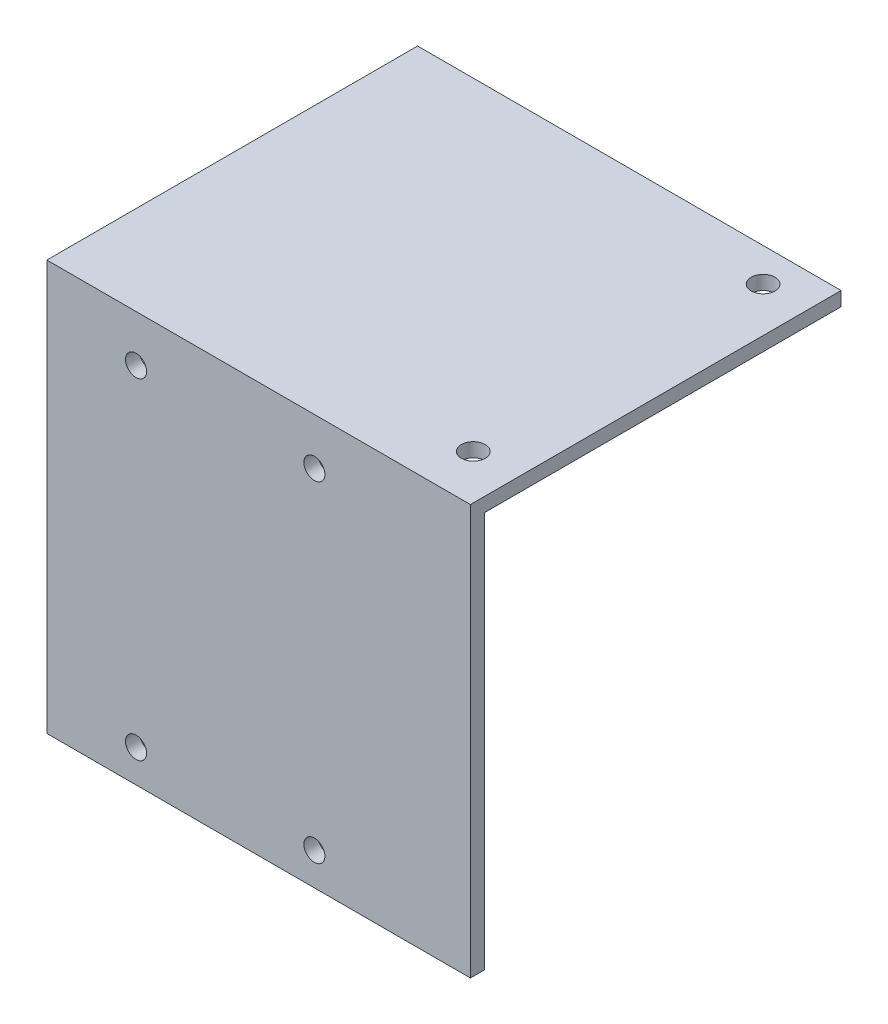
SolidWorks part; units mm, degrees
ref_plane "Front Plane" through (0, 0, 0) normal (0, 0, 1) x (1, 0, 0)
ref_plane "Top Plane" through (0, 0, 0) normal (0, 1, 0) x (1, 0, 0)
ref_plane "Right Plane" through (0, 0, 0) normal (1, 0, 0) x (0, 0, -1)
sketch "Sketch1" plane through (0, 0, 0) normal (0, 0, 1) x (1, 0, 0)
  line L0 (38.1, 51.75) -> (12.7, 51.75) construction
  line L1 (0, 58.4) -> (60.325, 58.4)
  line L2 (0, 58.4) -> (0, 0)
  line L3 (0, 0) -> (60.325, 0)
  line L4 (60.325, 58.4) -> (60.325, 0)
  line L6 (12.7, 51.75) -> (12.7, 4.65) construction
  line L8 (12.7, 4.65) -> (38.1, 4.65) construction
  line L9 (38.1, 51.75) -> (38.1, 4.65) construction
  circle A4 centre (12.7, 51.75) radius 1.5
  circle A5 centre (38.1, 51.75) radius 1.5
  circle A6 centre (12.7, 4.65) radius 1.5
  circle A7 centre (38.1, 4.65) radius 1.5
  point P5 (0, 0)
  point P7 (0, 0)
  point P8 (0, 0)
  dimension "D3" = 3
  dimension "D1" = 58.4
  dimension "D2" = 60.325
  dimension "D4" = 47.1
  dimension "D6" = 4.65
  dimension "D7" = 25.4
  dimension "D9" = 12.7
extrude "Boss-Extrude1" add sketch "Sketch1" against normal blind 2
sketch "Sketch2" plane through (0, 0, -2) normal (0, 0, -1) x (-1, 0, 0)
  line L0 (0, 58.4) -> (0, 56.4)
  line L1 (0, 58.4) -> (0, 0) construction
  line L2 (0, 56.4) -> (-60.325, 56.4)
  line L3 (-60.325, 56.4) -> (-60.325, 58.4)
  line L4 (-60.325, 58.4) -> (0, 58.4) construction
  line L5 (-60.325, 58.4) -> (0, 58.4)
  dimension "D1" = 60.325
  dimension "D2" = 2
extrude "Boss-Extrude2" add sketch "Sketch2" along normal blind 50.8
sketch "Sketch3" plane through (0, 58.4, 0) normal (0, 1, 0) x (1, 0, 0)
  line L0 (53.975, 48.0375) -> (53.975, 6.7625) construction
  line L1 (0, 52.8) -> (60.325, 52.8) construction
  line L2 (60.325, 52.8) -> (60.325, 0) construction
  circle A0 centre (53.975, 48.0375) radius 1.7
  circle A1 centre (53.975, 6.7625) radius 1.7
  dimension "D1" = 3.4
  dimension "D2" = 41.275
  dimension "D3" = 4.7625
  dimension "D4" = 6.35
extrude "Cut-Extrude1" cut sketch "Sketch3" against normal through all
